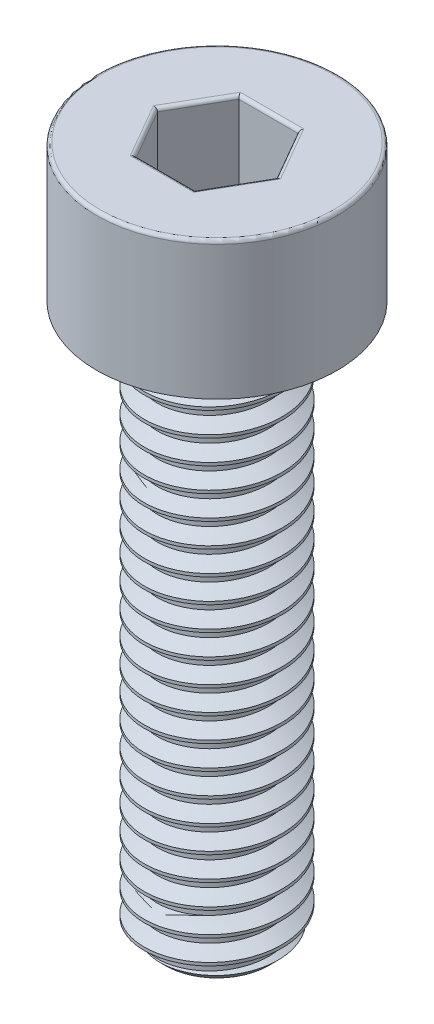
SolidWorks part; units mm, degrees
material "AISI 304"
ref_plane "Plano frontal" through (0, 0, 0) normal (0, 0, 1) x (1, 0, 0)
ref_plane "Plano superior" through (0, 0, 0) normal (0, 1, 0) x (1, 0, 0)
ref_plane "Plano direito" through (0, 0, 0) normal (1, 0, 0) x (0, 0, -1)
sketch "Esboço1" plane through (0, 0, 0) normal (0, 1, 0) x (1, 0, 0)
  circle A0 centre (0, 0) radius 3.5
  dimension "D1" = 7
extrude "Ressalto-extrusão1" add sketch "Esboço1" along normal blind 4 contours A0
sketch "Esboço3" plane through (0, 4, 0) normal (0, 1, 0) x (1, 0, 0)
  line L1 (1.7321, 0) -> (0.866, 1.5)
  line L2 (0.866, 1.5) -> (-0.866, 1.5)
  line L3 (-0.866, 1.5) -> (-1.7321, 0)
  line L4 (-1.7321, 0) -> (-0.866, -1.5)
  line L5 (-0.866, -1.5) -> (0.866, -1.5)
  line L6 (0.866, -1.5) -> (1.7321, 0)
  circle A0 centre (0, 0) radius 1.5 construction
  dimension "D1" = 3
extrude "Corte-extrusão1" cut sketch "Esboço3" against normal blind 3.5
chamfer "Chanfro3" distance 0.45 angle 70 6 edges at (0, 0.5, 1.5) (-1.299, 0.5, 0.75) (-1.299, 0.5, -0.75) (0, 0.5, -1.5) (1.299, 0.5, -0.75) (1.299, 0.5, 0.75) first distance on face at (0, 2.25, 1.5) first distance on face at (-1.299, 2.25, 0.75) first distance on face at (-1.299, 2.25, -0.75) first distance on face at (0, 2.25, -1.5) first distance on face at (1.299, 2.25, -0.75) first distance on face at (1.299, 2.25, 0.75)
fillet "Filete1" radius 0.1 7 edges at (0, 4, 3.5) (1.299, 4, -0.75) (0, 4, -1.5) (-1.299, 4, -0.75) (-1.299, 4, 0.75) (0, 4, 1.5) (1.299, 4, 0.75)
sketch "Esboço4" plane through (0, 0, 0) normal (0, -1, 0) x (1, 0, 0)
  circle A0 centre (0, 0) radius 2
  dimension "D1" = 4
extrude "Ressalto-extrusão2" add sketch "Esboço4" along normal blind 16
chamfer "Chanfro4" distance 0.5 angle 45 1 edges at (0, -16, -2)
fillet "Filete2" radius 0.2 1 edges at (0, 0, -2)
thread "Rosca1" pitch 0.7 method cut profile "Perfil da rosca1" start angle 0, offset 0, length 0, pitch 0.7, diameter 4
ref_plane "Plano1" through (-2, -0.2, 0) normal (0, 0, 1) x (-1, 0, 0)
sketch "Perfil da rosca1" plane through (-2, -0.2, 0) normal (0, 0, 1) x (-1, 0, 0)
  line L0 (0, 0) -> (0, 0.7) construction
  line L11 (0, 0) -> (0, 0.6125)
  line L12 (0, 0.6125) -> (-0.3789, 0.3937)
  line L13 (-0.3789, 0.3937) -> (-0.3789, 0.2187)
  line L15 (-0.3789, 0.2187) -> (0, 0)
  line L17 (-0.3789, 0.3062) -> (0, 0.3062) construction
  point P2 (0, 0)
  dimension "Pitch" = 0.7
  dimension "Profile_Angle" = 60
  dimension "Profile_Land" = 0.175
  dimension "Profile_Height" = 0.3789
